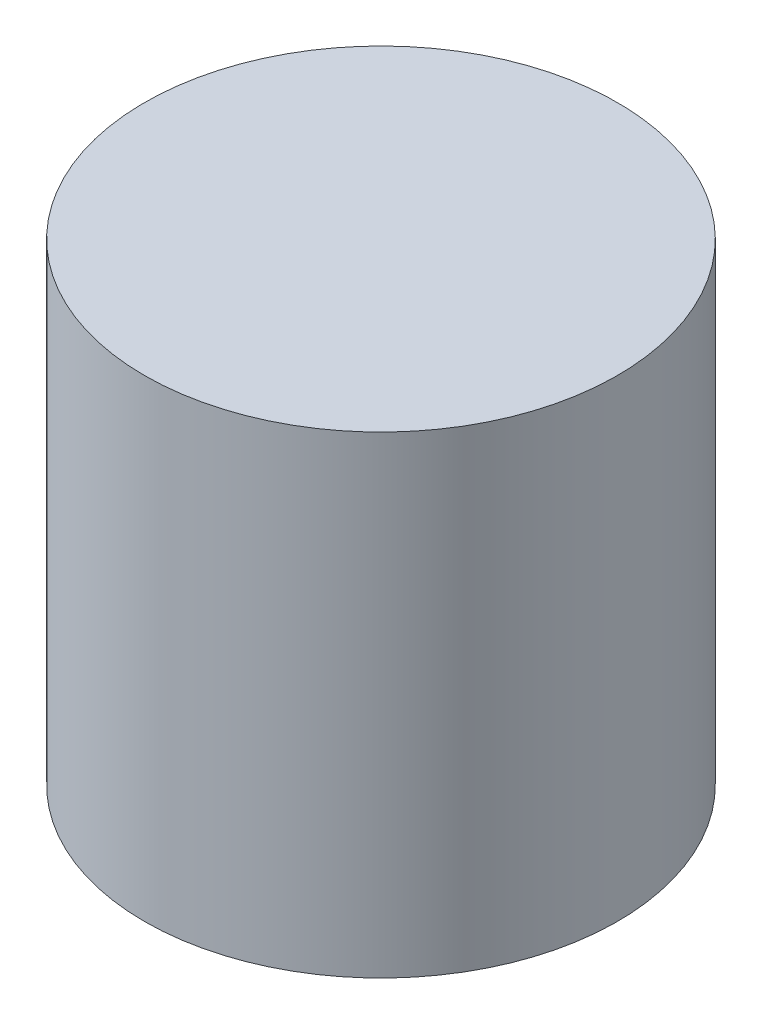
SolidWorks part; units mm, degrees
ref_plane "Front Plane" through (0, 0, 0) normal (0, 0, 1) x (1, 0, 0)
ref_plane "Top Plane" through (0, 0, 0) normal (0, 1, 0) x (1, 0, 0)
ref_plane "Right Plane" through (0, 0, 0) normal (1, 0, 0) x (0, 0, -1)
sketch "Sketch1" plane through (0, 0, 0) normal (0, 1, 0) x (1, 0, 0)
  circle A0 centre (0, 0) radius 6.35
  dimension "D1" = 12.7
extrude "Boss-Extrude1" add sketch "Sketch1" along normal blind 12.7
equation "\"R\"= 1.5in'radius of rotor"
equation "\"E\"= .125in'eccentricity"
equation "\"R_r\"= .25in'radius of roller"
equation "\"N\"= 8'number of rollers"
equation "\"R_o\"= .125in'output disk pin diameter"
equation "\"D1@Sketch1\"=2*\"R_r\""
